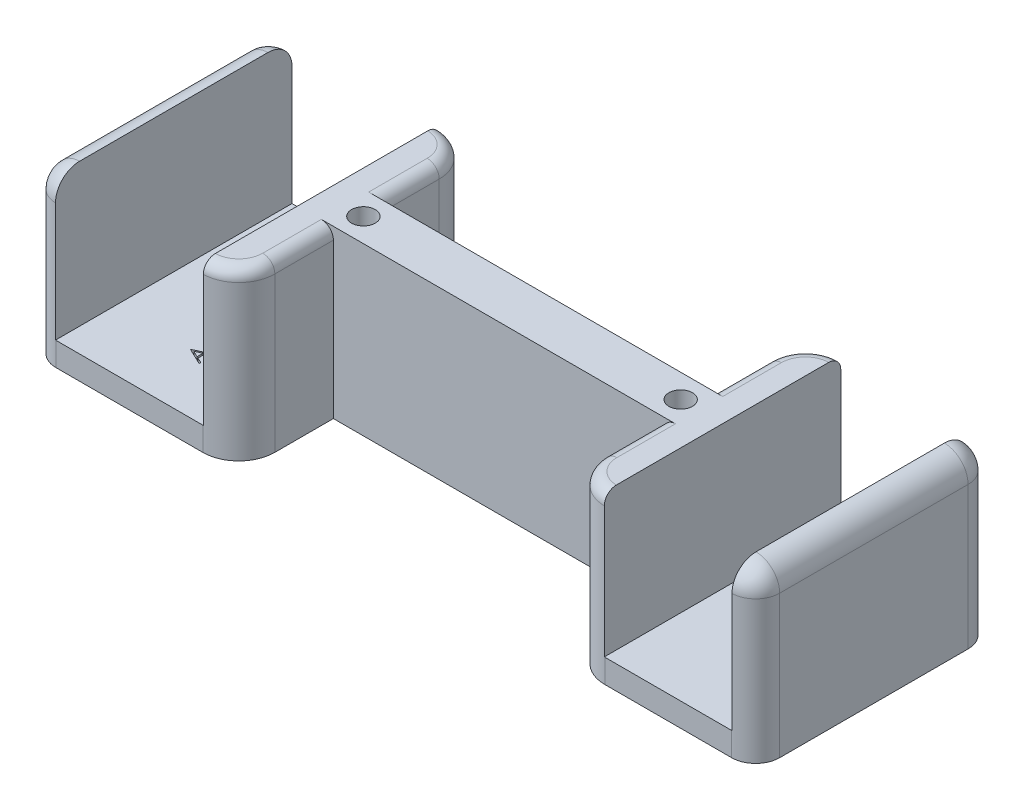
SolidWorks part; units mm, degrees
ref_plane "Front Plane" through (0, 0, 0) normal (0, 0, 1) x (1, 0, 0)
ref_plane "Top Plane" through (0, 0, 0) normal (0, 1, 0) x (1, 0, 0)
ref_plane "Right Plane" through (0, 0, 0) normal (1, 0, 0) x (0, 0, -1)
sketch "Sketch1" plane through (0, 0, 0) normal (0, 0, 1) x (1, 0, 0)
  line L1 (34.895, -12.605) -> (-34.895, -12.605)
  line L2 (34.895, -12.605) -> (34.895, 12.605)
  line L3 (34.895, 12.605) -> (-34.895, 12.605)
  line L4 (-34.895, -12.605) -> (-34.895, 12.605)
  line L5 (34.895, -12.605) -> (-34.895, 12.605) construction
  line L6 (34.895, 12.605) -> (-34.895, -12.605) construction
  point P0 (0, 0)
  dimension "D1" = 69.7901
  dimension "D2" = 25.21
sketch "Sketch2" plane through (0, 0, 0) normal (0, 0, 1) x (1, 0, 0)
  line L6 (44.895, 12.605) -> (44.895, 22.605)
  line L8 (-34.895, -12.605) -> (44.895, -12.605)
  line L9 (-34.895, -12.605) -> (-34.895, 22.605)
  line L10 (-34.895, 22.605) -> (44.895, 22.605)
  line L11 (44.895, -12.605) -> (44.895, 22.605)
extrude "Boss-Extrude2" add sketch "Sketch2" along normal blind 5 and the other way blind 5 contours L8 L11 L6 L10 L9 region at (5, 5, 0)
sketch "Sketch3" plane through (0, 0, 5) normal (0, 0, 1) x (1, 0, 0)
  point P9 (5, 5)
sketch "Sketch4" plane through (0, 0, 5) normal (0, 0, 1) x (1, 0, 0)
  line L0 (44.895, 5) -> (-34.895, 5)
  line L1 (-34.895, -12.605) -> (-34.895, 12.605) construction
  line L2 (5, -12.605) -> (5, 22.605)
  line L3 (-34.895, 22.605) -> (44.895, 22.605) construction
  line L4 (-34.895, 22.605) -> (-29.895, 22.605)
  line L5 (44.895, 22.605) -> (39.895, 22.605)
  line L6 (-32.395, 22.605) -> (-32.395, -12.605)
  line L7 (34.895, -12.605) -> (-34.895, -12.605) construction
  line L8 (42.395, 22.605) -> (42.395, -12.605)
  line L9 (-34.895, -12.605) -> (44.895, -12.605) construction
  circle A0 centre (-32.395, 5) radius 1.27
  circle A1 centre (42.395, 5) radius 1.27
  point P6 (5, 5)
  point P12 (5, 5)
  point P24 (-32.395, 5)
  point P26 (42.395, 5)
  dimension "D1" = 5
  dimension "D2" = 5
sketch "Sketch5" plane through (0, -12.605, 0) normal (0, -1, 0) x (1, 0, 0)
  line L0 (-34.895, -5) -> (-34.895, 5) construction
  line L2 (71.895, -25) -> (-61.895, -25)
  line L5 (71.895, -25) -> (71.895, 25)
  line L6 (71.895, 25) -> (-61.895, 25)
  line L7 (-61.895, -25) -> (-61.895, 25)
  line L8 (71.895, -25) -> (-61.895, 25) construction
  line L9 (71.895, 25) -> (-61.895, -25) construction
  line L10 (-61.895, 25) -> (-34.895, 25)
  line L11 (-61.895, 25) -> (-61.895, -25)
  line L12 (-61.895, -25) -> (-34.895, -25)
  line L13 (-34.895, 25) -> (-34.895, -25)
  line L14 (71.895, -25) -> (44.895, -25)
  line L15 (71.895, -25) -> (71.895, 25)
  line L16 (71.895, 25) -> (44.895, 25)
  line L17 (44.895, -25) -> (44.895, 25)
  point P0 (5, 0)
  point P5 (5, 0)
  line M12 (44.895, -5) -> (44.895, 5)
  line M14 (-34.895, 5) -> (-34.895, -5)
  dimension "D1" = 50
  dimension "D2" = 27
extrude "Boss-Extrude3" add sketch "Sketch5" against normal blind 5 contours L13 L6 L7 L2 M14 | L17 L2 L5 L6 M12 region at (58.395, -12.605, 0) region at (-48.395, -12.605, 0)
sketch "Sketch6" plane through (0, -12.605, 0) normal (0, -1, 0) x (1, 0, 0)
  line L0 (74.395, -25) -> (79.395, -25)
  line L1 (5, 5) -> (5, 21.2088) construction
  line L2 (44.895, 5) -> (-34.895, 5) construction
  line L9 (71.895, -25) -> (74.395, -25)
  line L10 (71.895, -25) -> (71.895, 25)
  line L11 (71.895, 25) -> (74.395, 25)
  line L12 (74.395, -25) -> (74.395, 25)
  line L15 (79.395, 25) -> (79.395, -25)
  line L16 (74.395, 25) -> (79.395, 25)
  line L17 (74.395, 25) -> (74.395, -25)
  line L18 (-34.895, -25) -> (-61.895, -25) construction
  line L19 (-34.895, 25) -> (-37.395, 25)
  line L20 (-34.895, 25) -> (-34.895, -25)
  line L21 (-34.895, -25) -> (-37.395, -25)
  line L22 (-37.395, 25) -> (-37.395, -25)
  line L23 (44.895, -25) -> (47.395, -25)
  line L24 (47.395, 25) -> (47.395, -25)
  line L25 (44.895, 25) -> (47.395, 25)
  line L26 (44.895, 25) -> (44.895, -25)
  line L27 (-68.645, 25) -> (-68.645, -25)
  line L28 (-73.645, 25) -> (-68.645, 25)
  line L30 (-68.645, 25) -> (-68.645, -25)
  line L31 (-68.645, -25) -> (-73.645, -25)
  line L32 (-73.645, 25) -> (-73.645, -25)
  line L33 (-68.645, 25) -> (-61.895, 25)
  line L35 (-68.645, 25) -> (-68.645, -25)
  line L37 (-61.895, 25) -> (-61.895, -25)
  line L38 (-61.895, -25) -> (-68.645, -25)
  line M9 (44.895, -25) -> (71.895, -25)
  line M10 (71.895, -25) -> (71.895, 25)
  line M11 (71.895, 25) -> (44.895, 25)
  line M16 (-61.895, 25) -> (-61.895, -25)
  dimension "D3" = 2.5
  dimension "D4" = 31.25
  dimension "D5" = 5
extrude "Boss-Extrude5" add sketch "Sketch6" against normal blind 5 contours M16 | L9 L12 L11 M10 | L24 M11 M9 M10 | L30 L28 L32 L31 region at (73.145, -12.605, 0) region at (59.645, -12.605, 0) region at (-65.27, -12.605, 0)
extrude "Boss-Extrude6" add sketch "Sketch6<3>" against normal up to surface (35.21 mm away) contours L16 L12 L0 L15 | L22 L21 L20 L19 | L26 L23 L24 L25 region at (76.895, -12.605, 0) up to face at (5, 22.605, 0)
sketch "Sketch6<3>" plane through (0, -12.605, 0) normal (0, -1, 0) x (1, 0, 0) same geometry as "Sketch6"
fillet "Fillet1" radius 5.08 1 edges at (79.395, 22.605, 0)
sketch "Sketch9" plane through (0, 22.605, 0) normal (0, 1, 0) x (1, 0, 0)
  line L1 (-37.395, 25) -> (47.395, 25)
  line L2 (-37.395, 25) -> (-37.395, -25)
  line L3 (-37.395, -25) -> (47.395, -25)
  line L4 (47.395, 25) -> (47.395, -25)
  dimension "D1" = 50
  dimension "D2" = 84.7901
extrude "Boss-Extrude9" [suppressed] add sketch "Sketch9" along normal blind 2.5
sketch "Sketch10" plane through (0, 22.605, 0) normal (0, 1, 0) x (1, 0, 0)
  circle A0 centre (-28.545, 0) radius 2.5
  circle A1 centre (38.545, 0) radius 2.5
  point P10 (-28.545, 0)
  dimension "D5" = 5
extrude "Cut-Extrude1" cut sketch "Sketch10" against normal blind 12.5
sketch "Sketch11" plane through (0, -12.605, 0) normal (0, -1, 0) x (1, 0, 0)
  line L0 (-34.895, -25) -> (-29.895, -25)
  line L1 (5, 5) -> (5, 23.7487) construction
  line L2 (-34.895, 25) -> (-29.895, 25)
  line L3 (-34.895, 25) -> (-34.895, -25)
  line L4 (-34.895, -25) -> (-29.895, -25)
  line L5 (-29.895, 25) -> (-29.895, -25)
  line L6 (-34.895, 5) -> (44.895, 5) construction
  line L7 (44.895, -25) -> (39.895, -25)
  line L8 (39.895, 25) -> (39.895, -25)
  line L9 (44.895, 25) -> (39.895, 25)
  line L10 (44.895, 25) -> (44.895, -25)
  dimension "D1" = 5
extrude "Boss-Extrude10" add sketch "Sketch11" against normal up to surface (35.21 mm away) contours L3 L2 L5 L4 | L7 L8 L9 L10 up to face at (-28.545, 22.605, 2.5)
sketch "Sketch12" plane through (0, 22.605, 0) normal (0, 1, 0) x (1, 0, 0)
  circle A0 centre (-28.545, 0) radius 2.5
  circle A1 centre (38.545, 0) radius 2.5
extrude "Cut-Extrude2" cut sketch "Sketch12" against normal up to surface (35.21 mm away) up to face at (4.2917, -12.605, 0)
fillet "Fillet2" radius 7.62 4 edges at (39.895, 5, -25) (39.895, 5, 25) (-29.895, 5, -25) (-29.895, 5, 25)
fillet "Fillet3" radius 2.54 8 edges at (42.0846, 22.605, 22.7256) (42.0846, 22.605, -22.7256) (-32.0846, 22.605, 22.7256) (-32.0846, 22.605, -22.7256) (39.895, 22.605, 11.19) (39.895, 22.605, -11.19) (-29.895, 22.605, 11.19) (-29.895, 22.605, -11.19)
fillet "Fillet4" radius 5.08 4 edges at (79.395, 2.4603, -25) (79.395, 2.4603, 25) (77.9353, 21.0893, -25) (77.9353, 21.0893, 25)
extrude "Boss-Extrude11" add sketch "Sketch6<4>" against normal up to surface (35.21 mm away) contours L28 L32 L31 L27 region at (-71.145, -12.605, 0) up to face at (38.545, 22.605, -2.5)
sketch "Sketch6<4>" plane through (0, -12.605, 0) normal (0, -1, 0) x (1, 0, 0) same geometry as "Sketch6"
fillet "Fillet5" radius 5.08 2 edges at (-73.645, 5, 25) (-73.645, 5, -25)
fillet "Fillet6" radius 5.08 3 edges at (-72.1853, 22.605, -23.4837) (-72.1853, 22.605, 23.4837) (-73.645, 22.605, 0)
sketch "Sketch13" plane through (0, -7.605, 0) normal (0, 1, 0) x (1, 0, 0)
  text T0 "AAA Battery\r\n"
  text T1 "9V Battery"
extrude "Cut-Extrude3" cut sketch "Sketch13" against normal blind 2.5
